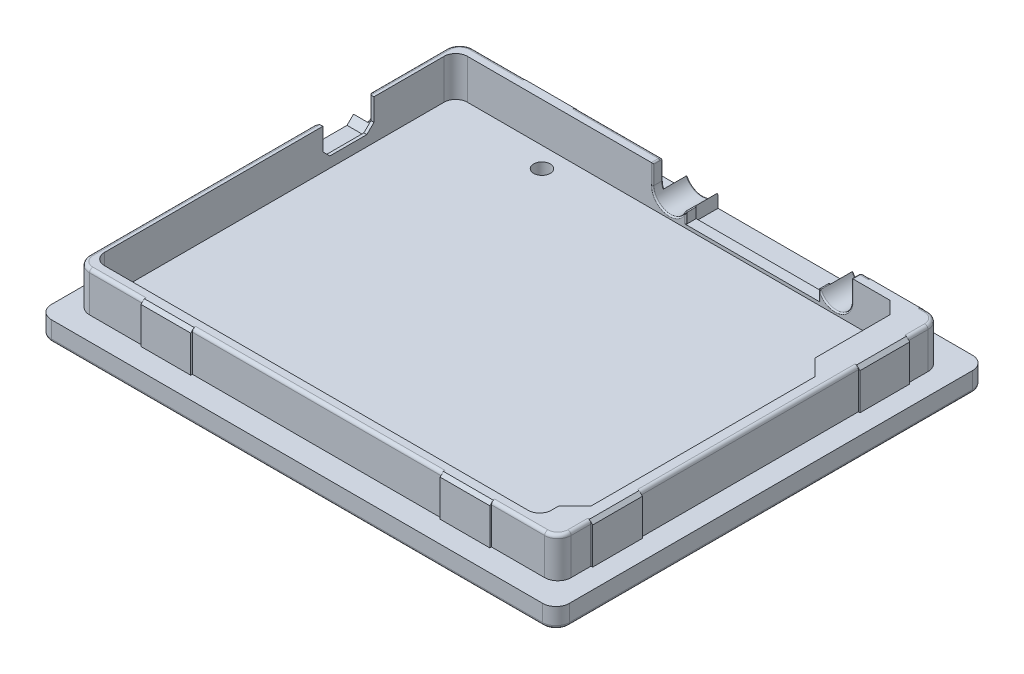
SolidWorks part; units mm, degrees
ref_plane "Front Plane" through (0, 0, 0) normal (0, 0, 1) x (1, 0, 0)
ref_plane "Top Plane" through (0, 0, 0) normal (0, 1, 0) x (1, 0, 0)
ref_plane "Right Plane" through (0, 0, 0) normal (1, 0, 0) x (0, 0, -1)
sketch "Sketch1" plane through (0, 0, 0) normal (0, 1, 0) x (1, 0, 0)
  line L0 (31.5158, 26.6) -> (32.93, 25.1858)
  line L1 (-31.93, -26.6) -> (31.93, -26.6)
  line L2 (-32.93, -25.6) -> (-32.93, 25.6)
  line L3 (-31.93, 26.6) -> (31.5158, 26.6)
  line L5 (-32.93, -26.6) -> (-32.9284, -25.6568) construction
  line L6 (-32.93, 26.6) -> (-32.9291, 25.5587) construction
  line L7 (32.93, 25.1858) -> (32.93, 13.85)
  line L8 (32.93, 13.85) -> (35.37, 11.41)
  line L9 (35.37, 11.41) -> (35.37, -21.71)
  line L10 (35.37, -21.71) -> (32.93, -24.15)
  line L11 (32.93, -24.15) -> (32.93, -25.6)
  line L12 (-32.93, 25.6) -> (-32.93, 26.6) construction
  line L13 (-32.93, 26.6) -> (-31.93, 26.6) construction
  line L14 (-32.93, 26.6) -> (32.93, -26.6) construction
  line L15 (-32.93, -25.6) -> (-32.93, -26.6) construction
  line L16 (-32.93, -26.6) -> (-31.93, -26.6) construction
  line L17 (-32.93, -26.6) -> (32.93, 26.6) construction
  line L18 (31.5158, 26.6) -> (32.93, 26.6) construction
  line L19 (32.93, 25.1858) -> (32.93, 26.6) construction
  arc A0 (-31.93, -26.6) -> (-32.93, -25.6) centre (-31.93, -25.6) cw
  arc A1 (-32.93, 25.6) -> (-31.93, 26.6) centre (-31.93, 25.6) cw
  arc A2 (32.93, -25.6) -> (31.93, -26.6) centre (31.93, -25.6) cw
  circle A3 centre (-17.63, 24.3) radius 1.575
  circle A4 centre (33.17, 8.9) radius 1.575
  circle A5 centre (33.17, -19) radius 1.575
  circle A6 centre (-19.13, -24.1) radius 1.575
  point P4 (0, 0)
  dimension "D2" = 1
  dimension "D9" = 1
  dimension "D10" = 3.15
  dimension "D1" = 53.2
  dimension "D3" = 2.44
  dimension "D4" = 135
  dimension "D5" = 68.3
  dimension "D6" = 2
  dimension "D7" = 12.75
  dimension "D8" = 2.45
  dimension "D11" = 2.3
  dimension "D12" = 27.9
  dimension "D13" = 15.3
  dimension "D14" = 7.6
  dimension "D15" = 0.24
  dimension "D16" = 2.5
  dimension "D17" = 13.8
sketch "Sketch2" plane through (0, 0, 0) normal (0, 1, 0) x (1, 0, 0)
  line L0 (-24.63, 28.9) -> (-32.63, 28.9)
  line L2 (-24.63, 28.9) -> (-24.63, 29.15)
  line L3 (-24.63, 29.15) -> (-17.13, 29.15)
  line L4 (-17.13, 28.9) -> (-17.13, 29.15)
  line L6 (27.47, 28.9) -> (27.47, 29.15)
  line L7 (27.47, 29.15) -> (34.97, 29.15)
  line L8 (34.97, 28.9) -> (34.97, 29.15)
  line L9 (-32.93, -25.6) -> (-32.93, 25.6) construction
  line L10 (35.97, -28.9) -> (27.97, -28.9)
  line L11 (37.97, -26.9) -> (37.97, -23.9)
  line L12 (35.97, 28.9) -> (34.97, 28.9)
  line L13 (-34.63, -26.9) -> (-34.63, 26.9)
  line L14 (37.97, -28.9) -> (-34.63, 28.9) construction
  line L15 (37.97, 28.9) -> (-34.63, -28.9) construction
  line L16 (-31.93, 26.6) -> (31.5158, 26.6) construction
  line L17 (-31.93, -26.6) -> (31.93, -26.6) construction
  line L18 (-31.93, -27.35) -> (31.93, -27.35)
  line L19 (33.68, -25.6) -> (33.68, -24.4607)
  line L20 (33.68, -24.4607) -> (36.12, -22.0207)
  line L21 (36.12, -22.0207) -> (36.12, 11.7207)
  line L22 (36.12, 11.7207) -> (33.68, 14.1607)
  line L23 (33.68, 14.1607) -> (33.68, 25.4964)
  line L24 (33.68, 25.4964) -> (31.8264, 27.35)
  line L25 (31.8264, 27.35) -> (-31.93, 27.35)
  line L26 (-33.68, 25.6) -> (-33.68, -25.6)
  line L27 (-31.93, -27.35) -> (31.93, -27.35)
  line L28 (33.68, -25.6) -> (33.68, -24.4607)
  line L29 (33.68, -24.4607) -> (36.12, -22.0207)
  line L30 (36.12, -22.0207) -> (36.12, 11.7207)
  line L31 (36.12, 11.7207) -> (33.68, 14.1607)
  line L32 (33.68, 14.1607) -> (33.68, 25.4964)
  line L33 (33.68, 25.4964) -> (31.8264, 27.35)
  line L34 (31.8264, 27.35) -> (-31.93, 27.35)
  line L35 (-33.68, 25.6) -> (-33.68, -25.6)
  line L36 (37.97, 23.9) -> (38.22, 23.9)
  line L38 (37.97, 16.4) -> (38.22, 16.4)
  line L39 (38.22, 23.9) -> (38.22, 16.4)
  line L40 (37.97, -16.4) -> (38.22, -16.4)
  line L42 (37.97, -23.9) -> (38.22, -23.9)
  line L43 (38.22, -16.4) -> (38.22, -23.9)
  line L45 (20.47, -28.9) -> (20.47, -29.15)
  line L46 (20.47, -29.15) -> (27.97, -29.15)
  line L47 (27.97, -28.9) -> (27.97, -29.15)
  line L49 (-24.63, -28.9) -> (-24.63, -29.15)
  line L50 (-24.63, -29.15) -> (-17.13, -29.15)
  line L51 (-17.13, -28.9) -> (-17.13, -29.15)
  line L52 (27.47, 28.9) -> (-17.13, 28.9)
  line L53 (37.97, 23.9) -> (37.97, 26.9)
  line L54 (37.97, -16.4) -> (37.97, 16.4)
  line L55 (20.47, -28.9) -> (-17.13, -28.9)
  line L56 (-24.63, -28.9) -> (-32.63, -28.9)
  line L57 (35.37, 11.41) -> (35.37, -21.71) construction
  arc A3 (37.97, 26.9) -> (35.97, 28.9) centre (35.97, 26.9) ccw
  arc A4 (35.97, -28.9) -> (37.97, -26.9) centre (35.97, -26.9) ccw
  arc A5 (-32.63, -28.9) -> (-34.63, -26.9) centre (-32.63, -26.9) cw
  arc A6 (31.93, -27.35) -> (33.68, -25.6) centre (31.93, -25.6) ccw
  arc A7 (-31.93, 27.35) -> (-33.68, 25.6) centre (-31.93, 25.6) ccw
  arc A8 (-33.68, -25.6) -> (-31.93, -27.35) centre (-31.93, -25.6) ccw
  arc A9 (31.93, -27.35) -> (33.68, -25.6) centre (31.93, -25.6) ccw
  arc A10 (-31.93, 27.35) -> (-33.68, 25.6) centre (-31.93, 25.6) ccw
  arc A11 (-33.68, -25.6) -> (-31.93, -27.35) centre (-31.93, -25.6) ccw
  arc A12 (-32.63, 28.9) -> (-34.63, 26.9) centre (-32.63, 26.9) ccw
  point P0 (1.67, 0)
  point P62 (38.095, -23.9)
  dimension "D6" = 2
  dimension "D2" = 1.7
  dimension "D3" = 2.3
  dimension "D4" = 2.3
  dimension "D5" = 2.6
  dimension "D7" = 7.5
  dimension "D8" = 10
  dimension "D9" = 10
  dimension "D10" = 5
  dimension "D11" = 5
  dimension "D12" = 3
  dimension "D13" = 10
  dimension "D14" = 0.25
  dimension "D1" = 0.75
extrude "Boss-Extrude1" add sketch "Sketch2" along normal blind 6
sketch "Sketch3" plane through (-34.63, 0, 0) normal (1, 0, 0) x (0, 0, -1)
  line L0 (14.915, 3.135) -> (28.9, 3.135) construction
  line L2 (-26.9, 0) -> (-23.9, 0) construction
  line L3 (13.915, 1.7) -> (8.415, 1.7)
  line L4 (14.915, 2.7) -> (14.915, 3.57)
  line L5 (13.915, 4.57) -> (8.415, 4.57)
  line L6 (7.415, 2.7) -> (7.415, 3.57)
  line L7 (14.915, 1.7) -> (7.415, 4.57) construction
  line L8 (14.915, 4.57) -> (7.415, 1.7) construction
  line L9 (8.415, 1.7) -> (7.415, 2.7)
  line L10 (14.915, 2.7) -> (13.915, 1.7)
  line L11 (28.9, 6) -> (28.9, 0) construction
  arc A0 (13.915, 4.57) -> (14.915, 3.57) centre (13.915, 3.57) cw
  arc A1 (7.415, 3.57) -> (8.415, 4.57) centre (8.415, 3.57) cw
  point P4 (11.165, 3.135)
  dimension "D5" = 1
  dimension "D1" = 13.985
  dimension "D2" = 7.5
  dimension "D3" = 1.7
  dimension "D4" = 2.87
sketch "Sketch4" plane through (-34.63, 0, 0) normal (1, 0, 0) x (0, 0, -1)
  line L11 (-26.9, 6) -> (-23.9, 6) construction
  line L12 (7.315, 6) -> (15.015, 6)
  line L16 (13.915, 4.67) -> (8.415, 4.67)
  line L17 (7.315, 3.57) -> (7.315, 2.6586)
  line L18 (7.315, 2.6586) -> (8.3736, 1.6)
  line L19 (8.3736, 1.6) -> (13.9564, 1.6)
  line L20 (13.9564, 1.6) -> (15.015, 2.6586)
  line L21 (15.015, 2.6586) -> (15.015, 3.57)
  line L23 (7.315, 6) -> (7.315, 2.6586)
  line L24 (7.315, 2.6586) -> (8.3736, 1.6)
  line L25 (8.3736, 1.6) -> (13.9564, 1.6)
  line L26 (13.9564, 1.6) -> (15.015, 2.6586)
  line L27 (15.015, 2.6586) -> (15.015, 6)
  arc A4 (8.415, 4.67) -> (7.315, 3.57) centre (8.415, 3.57) ccw
  arc A5 (15.015, 3.57) -> (13.915, 4.67) centre (13.915, 3.57) ccw
  dimension "D1" = 0.1
extrude "Cut-Extrude1" cut sketch "Sketch4" along normal up to next
sketch "Sketch10" plane through (-34.63, 0, 0) normal (-1, 0, 0) x (0, 0, 1)
  line L15 (-7.315, 6) -> (-7.315, 2.6586) construction
  line L16 (-7.315, 2.6586) -> (-8.3736, 1.6) construction
  line L17 (-8.3736, 1.6) -> (-13.9564, 1.6) construction
  line L18 (-13.9564, 1.6) -> (-15.015, 2.6586) construction
  line L19 (-15.015, 2.6586) -> (-15.015, 6) construction
  line L20 (-6.815, 6) -> (-6.815, 2.4515)
  line L21 (-6.815, 2.4515) -> (-8.1665, 1.1)
  line L22 (-8.1665, 1.1) -> (-14.1635, 1.1)
  line L23 (-14.1635, 1.1) -> (-15.515, 2.4515)
  line L24 (-15.515, 2.4515) -> (-15.515, 6)
  line L25 (-6.815, 6) -> (-6.815, 2.4515)
  line L26 (-6.815, 2.4515) -> (-8.1665, 1.1)
  line L27 (-8.1665, 1.1) -> (-14.1635, 1.1)
  line L28 (-14.1635, 1.1) -> (-15.515, 2.4515)
  line L29 (-15.515, 2.4515) -> (-15.515, 6)
  line L30 (-26.9, 6) -> (-15.015, 6) construction
  line L31 (-7.315, 6) -> (-7.315, 2.6586)
  line L32 (-7.315, 2.6586) -> (-8.3736, 1.6)
  line L33 (-8.3736, 1.6) -> (-13.9564, 1.6)
  line L34 (-13.9564, 1.6) -> (-15.015, 2.6586)
  line L35 (-15.015, 2.6586) -> (-15.015, 6)
  line L36 (-15.515, 6) -> (-15.015, 6)
  line L37 (-7.315, 6) -> (26.9, 6) construction
  line L38 (-7.315, 6) -> (-6.815, 6)
  dimension "D1" = 0.5
extrude "Cut-Extrude3" cut sketch "Sketch10" against normal blind 0.15
chamfer "Chamfer1" distance 0.35 distance2 0.5 5 edges at (-34.48, 4.3293, -7.315) (-34.48, 2.1293, -7.8443) (-34.48, 1.6, -11.165) (-34.48, 2.1293, -14.4857) (-34.48, 4.3293, -15.015) first distance on face at (-34.08, 4.3293, -7.315) first distance on face at (-34.08, 2.1293, -7.8443) first distance on face at (-34.08, 1.6, -11.165) first distance on face at (-34.08, 2.1293, -14.4857) first distance on face at (-34.08, 4.3293, -15.015)
sketch "Sketch7" plane through (0, 0, 0) normal (0, -1, 0) x (1, 0, 0)
  line L0 (37.97, 26.9) -> (37.97, 23.9) construction
  line L1 (-34.88, -32.4) -> (39.19, -32.4)
  line L2 (-36.88, -30.4) -> (-36.88, 30.4)
  line L3 (-34.88, 32.4) -> (39.19, 32.4)
  line L4 (41.19, -30.4) -> (41.19, 30.4)
  line L5 (-36.88, -32.4) -> (41.19, 32.4) construction
  line L6 (-36.88, 32.4) -> (41.19, -32.4) construction
  line L7 (27.97, 28.9) -> (35.97, 28.9) construction
  line L8 (-34.63, -26.9) -> (-34.63, 26.9) construction
  line L9 (35.97, -28.9) -> (34.97, -28.9) construction
  arc A0 (39.19, -32.4) -> (41.19, -30.4) centre (39.19, -30.4) ccw
  arc A1 (39.19, 32.4) -> (41.19, 30.4) centre (39.19, 30.4) cw
  arc A2 (-36.88, 30.4) -> (-34.88, 32.4) centre (-34.88, 30.4) cw
  arc A3 (-34.88, -32.4) -> (-36.88, -30.4) centre (-34.88, -30.4) cw
  circle A7 centre (-17.63, -24.3) radius 1.25
  circle A8 centre (33.17, -8.9) radius 1.25
  circle A9 centre (33.17, 19) radius 1.25
  circle A10 centre (-19.13, 24.1) radius 1.25
  point P0 (2.155, 0)
  dimension "D5" = 2
  dimension "D6" = 2.5
  dimension "D1" = 3.22
  dimension "D2" = 3.5
  dimension "D3" = 2.25
  dimension "D4" = 3.5
extrude "Boss-Extrude2" add sketch "Sketch7" along normal blind 3
sketch "Sketch8" plane through (-34.63, 0, 0) normal (-1, 0, 0) x (0, 0, 1)
  line L0 (-15.515, 2.4515) -> (-15.515, 0) construction
  line L1 (-26.9, 0) -> (26.9, 0) construction
  line L2 (-15.315, 0) -> (-7.015, 0)
  line L4 (-7.015, 2.2515) -> (-8.1665, 1.1)
  line L5 (-8.1665, 1.1) -> (-14.1635, 1.1)
  line L6 (-14.1635, 1.1) -> (-15.315, 2.2515)
  line L7 (-15.315, 2.2515) -> (-15.315, 0)
  line L8 (-7.015, 2.2515) -> (-7.015, 0)
  line L9 (-15.515, 2.4515) -> (-14.1635, 1.1) construction
  line L10 (-8.1665, 1.1) -> (-6.815, 2.4515) construction
  dimension "D1" = 0.2
extrude "Boss-Extrude3" add sketch "Sketch8" along normal up to surface (2.25 mm away) up to face at (-36.88, -1.5, 0)
sketch "Sketch9" plane through (0, 0, -28.9) normal (0, 0, -1) x (-1, 0, 0)
  line L0 (-35.47, 6) -> (-35.47, 0) construction
  line L1 (-35.97, 6) -> (-34.97, 6) construction
  line L2 (-35.97, 0) -> (-34.97, 0) construction
  line L4 (-26.02, 6) -> (3.98, 6)
  line L5 (-26.02, 3) -> (-26.02, 6)
  line L10 (3.98, 6) -> (3.98, 3)
  line L11 (-21.02, 3) -> (-21.02, 0.5)
  line L12 (-21.02, 0.5) -> (-1.02, 0.5)
  line L13 (-1.02, 3) -> (-1.02, 0.5)
  line L14 (-37.97, 6) -> (-37.97, 0) construction
  arc A0 (-1.02, 3) -> (3.98, 3) centre (1.48, 3) ccw
  arc A1 (-26.02, 3) -> (-21.02, 3) centre (-23.52, 3) ccw
  point P4 (-35.47, 3)
  dimension "D1" = 5
  dimension "D2" = 11.95
  dimension "D3" = 25
extrude "Cut-Extrude2" cut sketch "Sketch9" against normal up to next
sketch "Sketch12" plane through (0, 0, -28.9) normal (0, 0, -1) x (-1, 0, 0)
  line L0 (-35.97, 0) -> (-34.97, 0) construction
  line L1 (-25.82, 0) -> (-25.82, 2.0202)
  line L2 (-21.22, 0) -> (-25.82, 0)
  line L6 (-0.82, 0) -> (3.78, 0)
  line L10 (-34.97, 0) -> (-34.97, 6)
  line L11 (-34.97, 0) -> (-34.97, 6)
  line L12 (3.98, 3) -> (3.98, 6) construction
  line L14 (-34.97, 6) -> (-35.97, 6)
  line L15 (-35.97, 6) -> (-35.97, 0)
  line L16 (-35.97, 0) -> (-34.97, 0)
  line L30 (-21.22, 0) -> (-21.22, 2.0202)
  line L31 (-0.82, 2.0202) -> (-0.82, 0)
  line L32 (3.78, 0) -> (3.78, 2.0202)
  line L33 (-26.02, 6) -> (-26.02, 3) construction
  line L34 (-26.02, 3.0212) -> (-26.02, 4.0187) construction
  line L35 (-25.82, 1.0101) -> (-26.02, 1.0101) construction
  line L36 (-21.02, 0.5) -> (-21.22, 0.5) construction
  line L37 (-1.02, 0.5) -> (-0.82, 0.5) construction
  line L38 (3.78, 1.0101) -> (3.98, 1.0101) construction
  arc A0 (-1.02, 3) -> (3.98, 3) centre (1.48, 3) ccw construction
  arc A1 (-26.02, 3) -> (-21.02, 3) centre (-23.52, 3) ccw construction
  arc A2 (-0.82, 2.0202) -> (3.78, 2.0202) centre (1.48, 3) ccw
  arc A3 (-25.82, 2.0202) -> (-21.22, 2.0202) centre (-23.52, 3) ccw
  point P6 (-25.92, 3)
  point P24 (3.88, 3)
  dimension "D2" = 0.2
  dimension "D1" = 0
extrude "Boss-Extrude4" add sketch "Sketch12" along normal up to vertex (3.5 mm away) contours A3 L1 L2 L30 | A2 L31 L6 L32 region at (25.7698, 1.0101, -28.9) region at (0.7698, 1.0101, -28.9) up to point (39.19, 0, -32.4)
fillet "Fillet4" radius 0.1 2 edges at (1.02, 3, -28.125) (21.02, 3, -28.125)
fillet "Fillet5" radius 0.5 16 edges at (-34.63, 6, -21.2075) (-34.0442, 6, -28.3142) (-34.63, 6, 10.0425) (-34.0442, 6, 28.3142) (37.97, 6, 25.4) (37.3842, 6, 28.3142) (37.97, 6, -25.4) (35.47, 6, -28.9) (-10.555, 6, -28.9) (-28.63, 6, -28.9) (-28.63, 6, 28.9) (1.67, 6, 28.9) (31.97, 6, 28.9) (37.97, 6, 0) (26.745, 6, -28.9) (37.3842, 6, -28.3142)
chamfer "Chamfer5" distance 0.5 angle 45 6 edges at (38.22, 6, 20.15) (24.22, 6, 29.15) (-20.88, 6, 29.15) (-20.88, 6, -29.15) (31.22, 6, -29.15) (38.22, 6, -20.15)
fillet "Fillet1" radius 0.5 8 edges at (-36.2942, -3, -31.8142) (-36.88, -3, 0) (-36.2942, -3, 31.8142) (2.155, -3, 32.4) (40.6042, -3, 31.8142) (41.19, -3, 0) (40.6042, -3, -31.8142) (2.155, -3, -32.4)
fillet "Fillet2" radius 0.2 18 edges at (26.02, 4.5, -27.35) (-3.98, 4.5, -27.35) (24.0103, 0.5485, -27.35) (-1.9703, 0.5485, -27.35) (21.02, 1.25, -27.35) (21.1004, 2.0981, -27.35) (1.02, 1.25, -27.35) (0.9396, 2.0981, -27.35) (-3.9295, 2.5, -28.9) (25.9695, 2.5, -28.9) (-3.98, 4.25, -28.9) (26.02, 4.25, -28.9) (-1.48, 0.5, -32.4) (23.52, 0.5, -32.4) (-3.98, 6, -27.875) (-3.98, 5.8536, -28.7536) (26.02, 6, -27.875) (26.02, 5.8536, -28.7536)
chamfer "Chamfer3" distance 0.25 distance2 1 1 edges at (-35.755, 2.2515, -15.315) first distance on face at (-35.33, 1.9343, -14.9978)
chamfer "Chamfer4" distance 1 distance2 0.25 1 edges at (-35.755, 2.2515, -7.015) first distance on face at (-35.755, 1.1257, -7.015)
